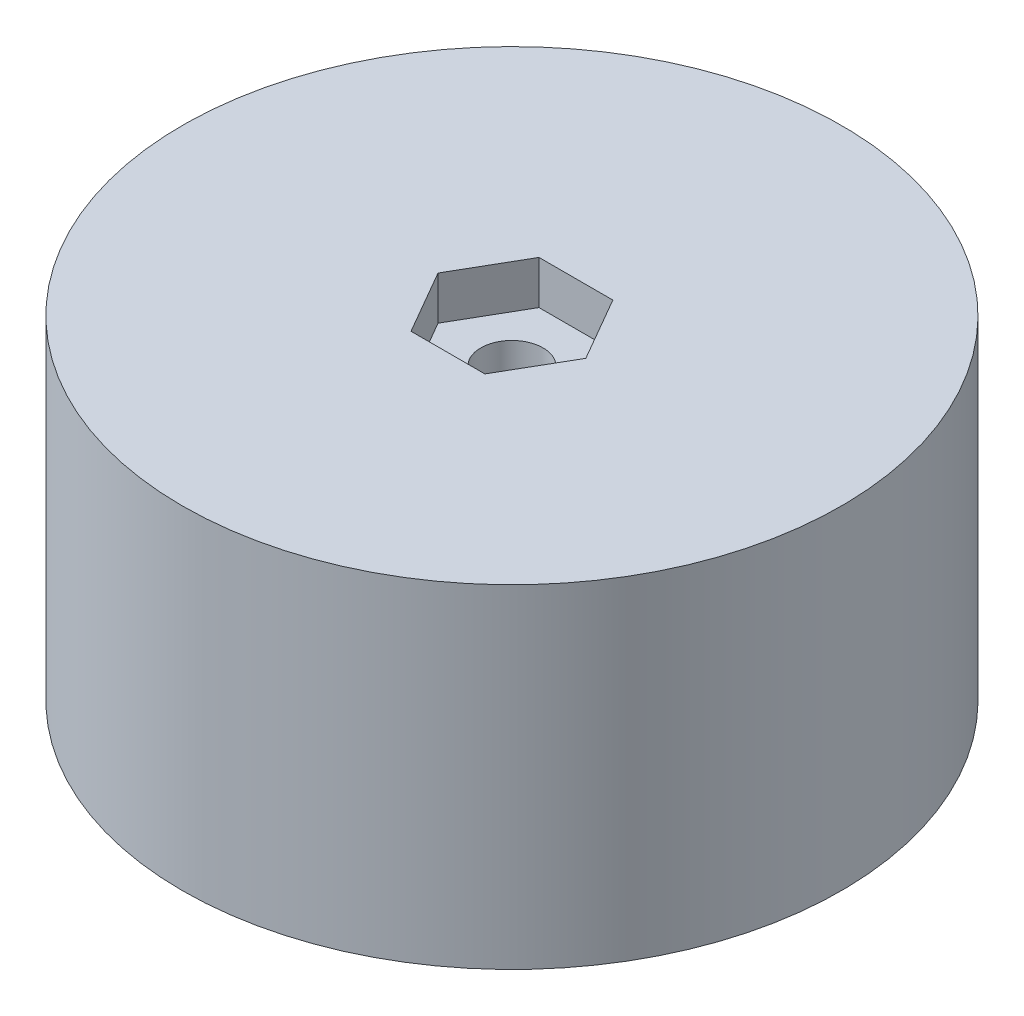
SolidWorks part; units mm, degrees
ref_plane "Front Plane" through (0, 0, 0) normal (0, 0, 1) x (1, 0, 0)
ref_plane "Top Plane" through (0, 0, 0) normal (0, 1, 0) x (1, 0, 0)
ref_plane "Right Plane" through (0, 0, 0) normal (1, 0, 0) x (0, 0, -1)
sketch "Sketch1" plane through (0, 0, 0) normal (0, 1, 0) x (1, 0, 0)
  circle A0 centre (0, 0) radius 22.75
  circle A1 centre (0, 0) radius 2.15
  dimension "D1" = 45.5
  dimension "D2" = 4.3
extrude "Boss-Extrude1" add sketch "Sketch1" along normal blind 23
sketch "Sketch2" plane through (0, 23, 0) normal (0, 1, 0) x (1, 0, 0)
  line L1 (5.1, 0) -> (2.55, 4.4167)
  line L2 (2.55, 4.4167) -> (-2.55, 4.4167)
  line L3 (-2.55, 4.4167) -> (-5.1, 0)
  line L4 (-5.1, 0) -> (-2.55, -4.4167)
  line L5 (-2.55, -4.4167) -> (2.55, -4.4167)
  line L6 (2.55, -4.4167) -> (5.1, 0)
  circle A0 centre (0, 0) radius 4.4167 construction
  dimension "D1" = 5.1
extrude "Cut-Extrude1" cut sketch "Sketch2" against normal blind 3
